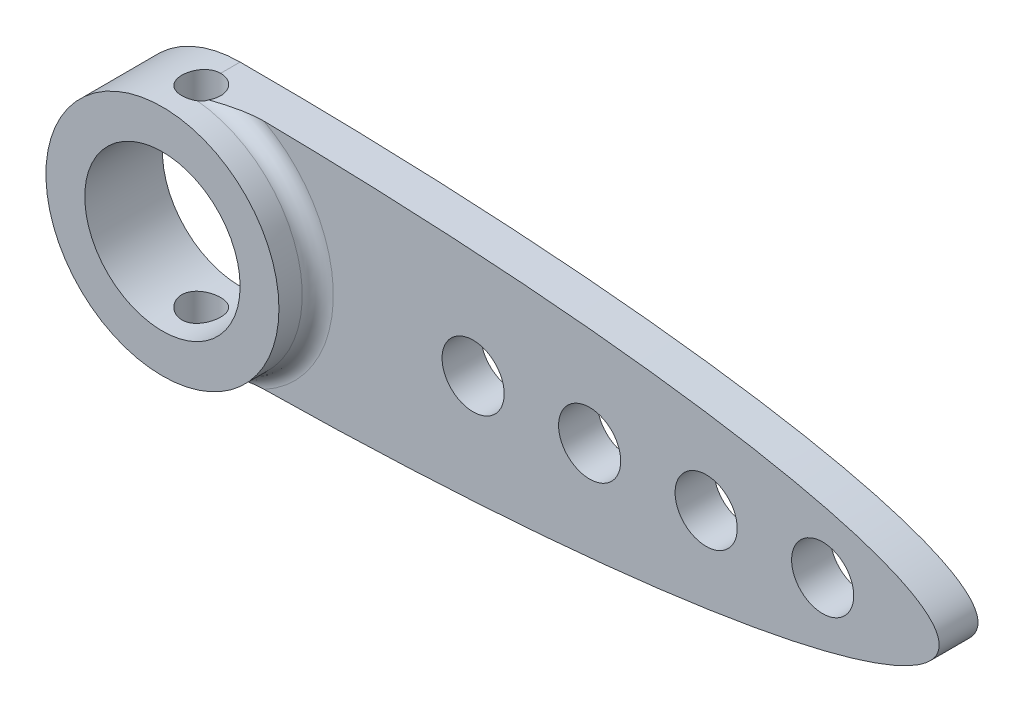
SolidWorks part; units mm, degrees
ref_plane "Front Plane" through (0, 0, 0) normal (0, 0, 1) x (1, 0, 0)
ref_plane "Top Plane" through (0, 0, 0) normal (0, 1, 0) x (1, 0, 0)
ref_plane "Right Plane" through (0, 0, 0) normal (1, 0, 0) x (0, 0, -1)
sketch "Sketch1" plane through (0, 0, 0) normal (0, 0, 1) x (1, 0, 0)
  line L0 (0, 0) -> (80, 0) construction
  circle A0 centre (0, 0) radius 10
  circle A1 centre (80, 0) radius 4
  arc A2 (0, 15) -> (0, -15) centre (0, 0) ccw
  circle A3 centre (65, 0) radius 4
  circle A4 centre (50, 0) radius 4
  circle A5 centre (35, 0) radius 4
  ellipse E0 centre (0, 0) end of major axis (-95, 0) minor radius 15 (0, -15) -> (0, 15) ccw
  dimension "D2" = 8
  dimension "D3" = 20
  dimension "D4" = 30
  dimension "D1" = 4
  dimension "D6" = 15
extrude "Boss-Extrude1" add sketch "Sketch1" along normal blind 5
sketch "Sketch2" plane through (0, 0, 5) normal (0, 0, 1) x (1, 0, 0)
  circle A0 centre (0, 0) radius 10
  circle A1 centre (0, 0) radius 15
extrude "Boss-Extrude2" add sketch "Sketch2" along normal blind 5
fillet "Fillet1" radius 2 1 edges at (15, 0, 5)
sketch "Sketch3" plane through (0, 0, 0) normal (0, 1, 0) x (1, 0, 0)
  line L0 (10, 0) -> (-10, 0) construction
  circle A0 centre (0, -5) radius 2.5
  dimension "D1" = 5
  dimension "D2" = 5
extrude "Cut-Extrude1" cut sketch "Sketch3" against normal through all and the other way through all
